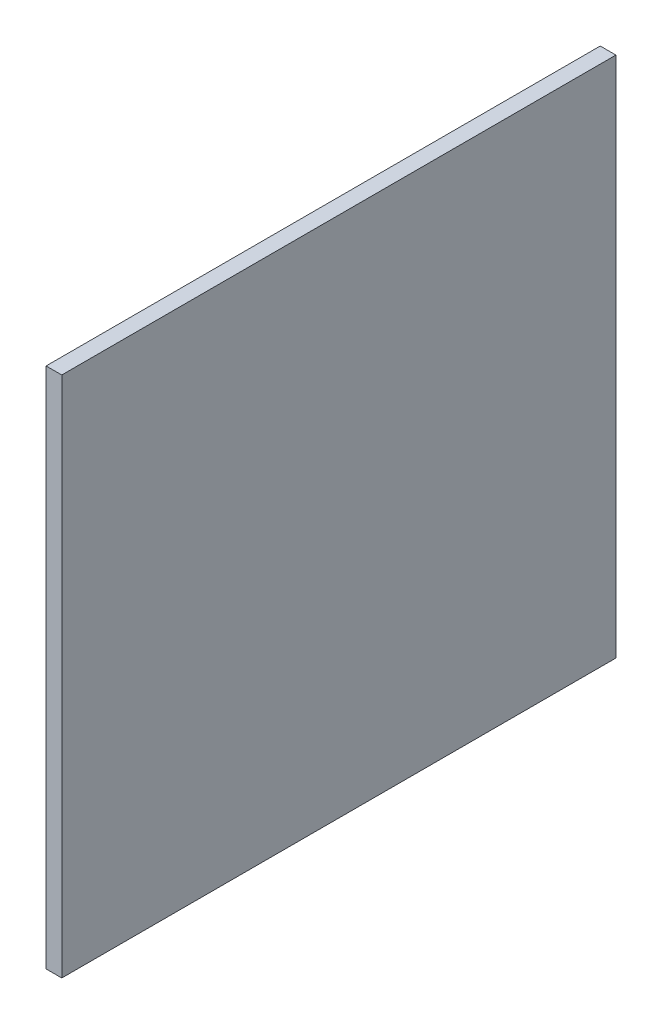
SolidWorks part; units mm, degrees
ref_plane "Front Plane" through (0, 0, 0) normal (1, 0, 0) x (0, 1, 0)
ref_plane "Top Plane" through (0, 0, 0) normal (0, 0, 1) x (0, 1, 0)
ref_plane "Right Plane" through (0, 0, 0) normal (0, 1, 0) x (-1, 0, 0)
sketch "Sketch1" plane through (0, 0, 0) normal (1, 0, 0) x (0, 1, 0)
  line L1 (-100, -106.11) -> (100, -106.11)
  line L2 (-100, -106.11) -> (-100, 106.11)
  line L3 (-100, 106.11) -> (100, 106.11)
  line L4 (100, -106.11) -> (100, 106.11)
  line L5 (-100, -106.11) -> (100, 106.11) construction
  line L6 (-100, 106.11) -> (100, -106.11) construction
  point P0 (0, 0)
  dimension "D1" = 200
  dimension "D2" = 212.22
extrude "Boss-Extrude1" add sketch "Sketch1" along normal blind 6 contours L1 L4 L3 L2
